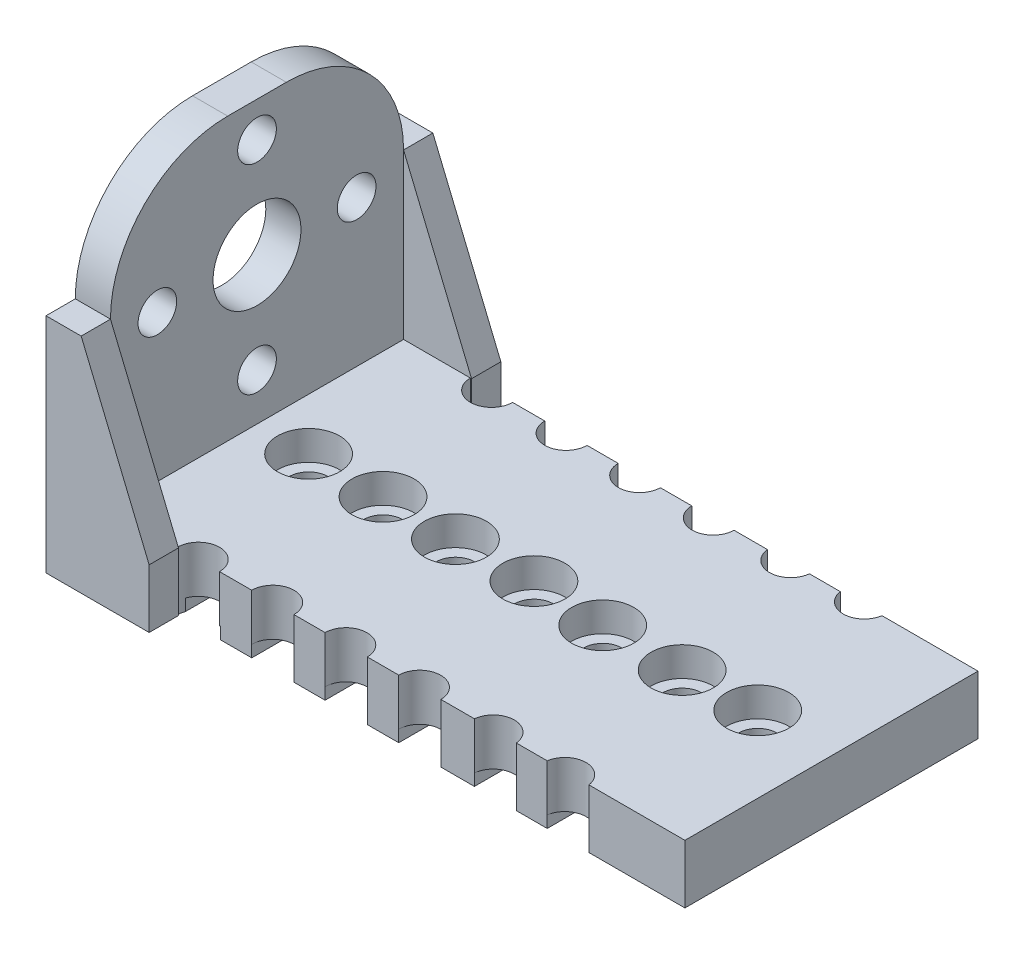
SolidWorks part; units mm, degrees
ref_plane "Plano frontal" through (0, 0, 0) normal (0, 0, 1) x (1, 0, 0)
ref_plane "Plano superior" through (0, 0, 0) normal (0, 1, 0) x (1, 0, 0)
ref_plane "Plano direito" through (0, 0, 0) normal (1, 0, 0) x (0, 0, -1)
sketch "Esboço1" plane through (0, 0, 0) normal (0, 1, 0) x (1, 0, 0)
  line L1 (-23.4634, 13.7439) -> (25.5366, 13.7439)
  line L2 (-23.4634, 13.7439) -> (-23.4634, -11.2561)
  line L3 (-23.4634, -11.2561) -> (25.5366, -11.2561)
  line L4 (25.5366, 13.7439) -> (25.5366, -11.2561)
  line L6 (-23.4634, -11.2561) -> (-26.4634, -11.2561)
  line L7 (-23.4634, -11.2561) -> (-23.4634, 13.7439)
  line L8 (-23.4634, 13.7439) -> (-26.4634, 13.7439)
  line L9 (-26.4634, -11.2561) -> (-26.4634, 13.7439)
  dimension "D1" = 49
  dimension "D2" = 25
extrude "Ressalto-extrusão2" add sketch "Esboço1" along normal blind 29 contours L6 L9 L8 L7
extrude "Ressalto-extrusão3" add sketch "Esboço1<4>" along normal blind 5 contours L4 L1 L2 L3 region at (1.0366, 0, -1.2439)
sketch "Esboço1<4>" plane through (0, 0, 0) normal (0, 1, 0) x (1, 0, 0) same geometry as "Esboço1"
ref_plane "Plano8" through (25.5366, 0, 11.2561) normal (0, -1, 0) x (-1, 0, 0)
sketch "Esboço6" plane through (-23.4634, 0, 0) normal (1, 0, 0) x (0, 0, -1)
  line L0 (1.2439, 29) -> (1.2439, 0) construction
  line L1 (1.2439, 17.5) -> (1.2439, 17.5)
  line L3 (-11.2561, 29) -> (13.7439, 29) construction
  line L4 (-11.2561, 0) -> (13.7439, 0) construction
  circle A0 centre (1.2439, 17.5) radius 3.75
  circle A1 centre (1.2439, 17.5) radius 8.5 construction
  circle A2 centre (9.7439, 17.5) radius 1.65
  circle A3 centre (-7.2561, 17.5) radius 1.65
  circle A4 centre (1.2439, 26) radius 1.65
  circle A5 centre (1.2439, 9) radius 1.65
fillet "Filete2" radius 10 1 edges at (-24.9634, 29, -13.7439) type face fillet first side face at (-24.9634, 29, -1.2439) second side face at (-12.2134, 13.3333, -13.7439)
fillet "Filete3" radius 10 1 edges at (-24.9634, 29, 11.2561) type face fillet first side face at (-24.9634, 29, 3.7561) second side face at (-12.2134, 13.3333, 11.2561)
sketch "Esboço8" plane through (0, 5, 0) normal (0, 1, 0) x (1, 0, 0)
  line L3 (-26.4634, 1.2439) -> (-19.0634, 1.2439) construction
  line L4 (-26.4634, -1.2561) -> (-26.4634, 3.7439) construction
  line L5 (-19.0634, 1.2439) -> (-12.7134, 1.2439) construction
  line L6 (-12.7134, 1.2439) -> (-6.3634, 1.2439) construction
  line L7 (-6.3634, 1.2439) -> (-0.0134, 1.2439) construction
  line L8 (-0.0134, 1.2439) -> (6.3366, 1.2439) construction
  line L9 (6.3366, 1.2439) -> (12.6866, 1.2439) construction
  line L10 (12.6866, 1.2439) -> (19.0366, 1.2439) construction
  circle A0 centre (-19.0634, 1.2439) radius 1.65
  circle A1 centre (-12.7134, 1.2439) radius 1.65
  circle A2 centre (-6.4973, 1.2033) radius 1.65
  circle A3 centre (-0.0509, 1.4513) radius 1.65
  circle A4 centre (6.1476, 1.1207) radius 1.65
  circle A5 centre (12.8419, 1.2033) radius 1.65
  circle A6 centre (19.0404, 1.4513) radius 1.65
extrude "Corte-extrusão5" cut sketch "Esboço8" against normal blind 5
sketch "Esboço9" plane through (0, 0, 0) normal (0, -1, 0) x (1, 0, 0)
  line L0 (-26.4634, 11.2561) -> (-15.9634, 11.2561) construction
  line L1 (25.5366, 11.2561) -> (-26.4634, 11.2561) construction
  line L2 (-15.9634, 11.2561) -> (-9.6134, 11.2561) construction
  line L3 (-9.6134, 11.2561) -> (-3.2634, 11.2561) construction
  line L4 (-3.2634, 11.2561) -> (3.0866, 11.2561) construction
  line L5 (3.0866, 11.2561) -> (9.4366, 11.2561) construction
  line L6 (9.4366, 11.2561) -> (15.7866, 11.2561) construction
  line L7 (-25.384, 11.4415) -> (-14.884, 11.4415) construction
  line L8 (-26.4634, -1.2439) -> (25.5366, -1.2439) construction
  line L10 (-26.4634, 11.2561) -> (-26.4634, -13.7439) construction
  line L11 (25.5366, -13.7439) -> (25.5366, 11.2561) construction
  line L12 (9.4366, -13.7439) -> (15.7866, -13.7439) construction
  line L13 (3.0866, -13.7439) -> (9.4366, -13.7439) construction
  line L14 (-3.2634, -13.7439) -> (3.0866, -13.7439) construction
  line L15 (-9.6134, -13.7439) -> (-3.2634, -13.7439) construction
  line L16 (-15.9634, -13.7439) -> (-9.6134, -13.7439) construction
  circle A0 centre (-15.9634, 11.2561) radius 1.8
  circle A1 centre (-9.6134, 11.2561) radius 1.8
  circle A2 centre (-3.3568, 11.2763) radius 1.8
  circle A3 centre (2.9244, 11.2763) radius 1.8
  circle A4 centre (9.3708, 11.4415) radius 1.8
  circle A5 centre (15.5692, 11.5242) radius 1.8
  circle A6 centre (15.5692, -14.012) radius 1.8
  circle A7 centre (9.3708, -13.9294) radius 1.8
  circle A8 centre (2.9244, -13.7641) radius 1.8
  circle A9 centre (-3.3568, -13.7641) radius 1.8
  circle A10 centre (-9.6134, -13.7439) radius 1.8
  circle A11 centre (-15.9634, -13.7439) radius 1.8
  dimension "D1" = 3.6
  dimension "D2" = 3.6
  dimension "D3" = 3.6
  dimension "D4" = 3.6
  dimension "D5" = 3.6
  dimension "D6" = 3.6
extrude "Corte-extrusão6" cut sketch "Esboço9" against normal blind 5
sketch "Esboço10" plane through (0, 0, 0) normal (0, -1, 0) x (1, 0, 0)
  line L1 (-17.6634, 11.2561) -> (-14.0634, 11.2561)
  line L2 (-17.6634, 11.2561) -> (-17.6634, -13.7439)
  line L3 (-17.6634, -13.7439) -> (-14.0634, -13.7439)
  line L4 (-14.0634, 11.2561) -> (-14.0634, -13.7439)
  line L5 (-11.4134, 11.2561) -> (-7.8134, 11.2561)
  line L6 (-11.4134, 11.2561) -> (-11.4134, -13.7439)
  line L7 (-11.4134, -13.7439) -> (-7.8134, -13.7439)
  line L8 (-7.8134, 11.2561) -> (-7.8134, -13.7439)
  line L9 (-5.1567, 11.2561) -> (-1.5569, 11.2561)
  line L10 (-5.1567, 11.2561) -> (-5.1567, -13.7439)
  line L11 (-5.1567, -13.7439) -> (-1.5569, -13.7439)
  line L12 (-1.5569, 11.2561) -> (-1.5569, -13.7439)
  line L13 (1.1245, 11.2561) -> (4.7242, 11.2561)
  line L14 (1.1245, 11.2561) -> (1.1245, -13.7439)
  line L15 (1.1245, -13.7439) -> (4.7242, -13.7439)
  line L16 (4.7242, 11.2561) -> (4.7242, -13.7439)
  line L17 (7.5803, 11.2561) -> (11.1612, 11.2561)
  line L18 (7.5803, 11.2561) -> (7.5803, -13.7439)
  line L19 (7.5803, -13.7439) -> (11.1612, -13.7439)
  line L20 (11.1612, 11.2561) -> (11.1612, -13.7439)
  line L21 (13.7893, 11.2561) -> (17.3492, 11.2561)
  line L22 (13.7893, 11.2561) -> (13.7893, -13.7439)
  line L23 (13.7893, -13.7439) -> (17.3492, -13.7439)
  line L24 (17.3492, 11.2561) -> (17.3492, -13.7439)
  dimension "D1" = 3.6
extrude "Corte-extrusão7" cut sketch "Esboço10" against normal blind 1
sketch "Esboço11" plane through (0, 5, 0) normal (0, 1, 0) x (1, 0, 0)
  circle A0 centre (-19.0634, 1.2439) radius 2.65
  circle A1 centre (-12.7134, 1.2439) radius 2.65
  circle A2 centre (-6.4973, 1.2033) radius 2.65
  circle A3 centre (-0.0509, 1.4513) radius 2.65
  circle A4 centre (6.1476, 1.1207) radius 2.65
  circle A5 centre (12.8419, 1.2033) radius 2.65
  circle A6 centre (19.0404, 1.4513) radius 2.65
extrude "Corte-extrusão8" cut sketch "Esboço11" against normal blind 2.5
extrude "Corte-extrusão9" cut sketch "Esboço6" against normal blind 10 contours A3 | A0 | A2 | A4 | A5
sketch "Esboço29" plane through (0, 0, 11.2561) normal (0, 0, 1) x (1, 0, 0)
  line L0 (-23.4634, 19) -> (-17.6634, 5)
  line L1 (-17.6634, 5) -> (-17.6634, 0)
  line L2 (-17.6634, 0) -> (-26.4634, 0)
  line L3 (-26.4634, 0) -> (-26.4634, 19)
  line L4 (-26.4634, 19) -> (-23.4634, 19)
extrude "Ressalto-extrusão4" add sketch "Esboço29" along normal blind 2.5
sketch "Esboço30" plane through (0, 0, -13.7439) normal (0, 0, -1) x (-1, 0, 0)
  line L0 (23.4634, 19) -> (17.6634, 5)
  line L1 (17.6634, 5) -> (17.6634, 0)
  line L2 (17.6634, 0) -> (26.4634, 0)
  line L3 (26.4634, 0) -> (26.4634, 19)
  line L4 (26.4634, 19) -> (23.4634, 19)
extrude "Ressalto-extrusão5" add sketch "Esboço30" along normal blind 2.5
